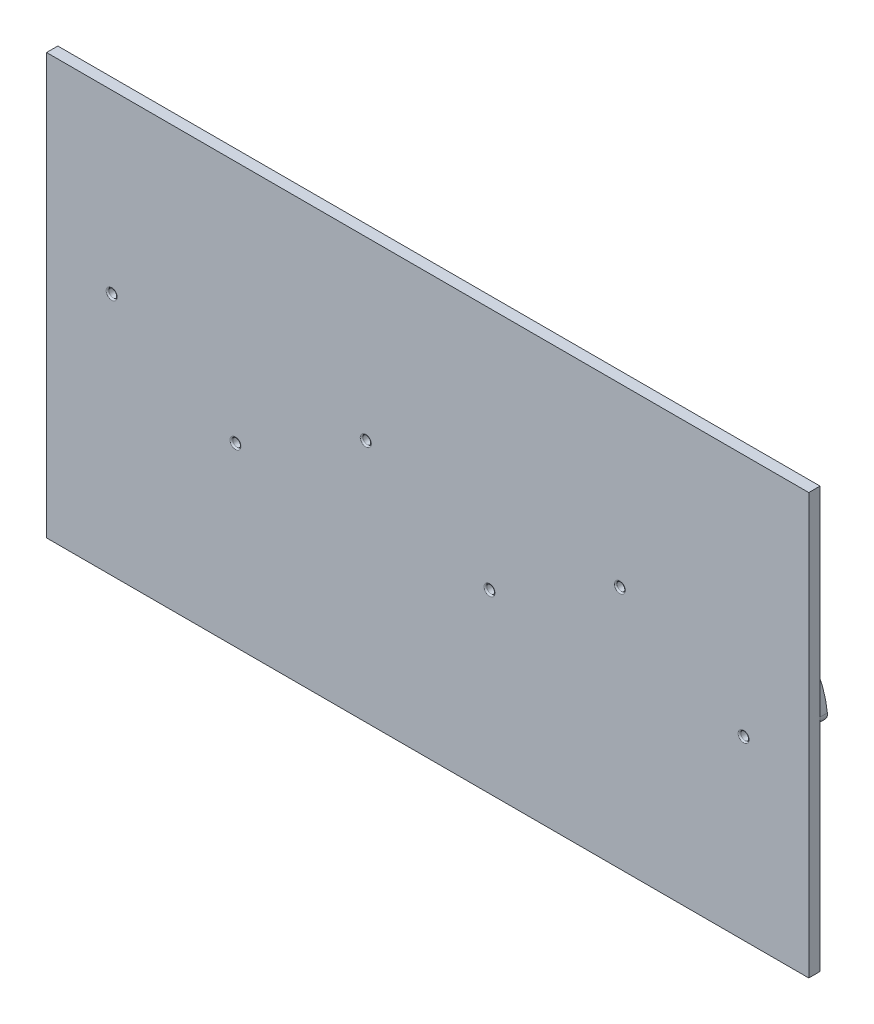
SolidWorks part; units mm, degrees
ref_plane "Front" through (0, 0, 0) normal (0, 0, 1) x (1, 0, 0)
ref_plane "Top" through (0, 0, 0) normal (0, 1, 0) x (1, 0, 0)
ref_plane "Right" through (0, 0, 0) normal (1, 0, 0) x (0, 0, -1)
sketch "Sketch1" plane through (0, 0, 0) normal (0, 0, 1) x (1, 0, 0)
  line L0 (0, 0) -> (0, 155.4998) construction
  line L1 (0, 0) -> (0, -147.6375) construction
  line L2 (0, 25.4) -> (-281.6343, 25.4) construction
  line L3 (0, -25.4) -> (-306.3875, -25.4) construction
  line L4 (-92.1, 25.4) -> (-92.1, -160.4472) construction
  line L5 (0, 25.4) -> (-92.1, 25.4)
  line L6 (-92.1, 25.4) -> (-92.1, -25.4)
  line L7 (-92.1, -25.4) -> (0, -25.4)
  line L8 (0, -25.4) -> (0, 25.4)
  point P3 (0, 25.4)
  point P5 (0, -25.4)
  point P11 (-92.1, 25.4)
  point P14 (-92.1, -25.4)
  dimension "D1" = 25.4
  dimension "W" = 25.4
  dimension "Len" = 92.1
extrude "Extrude1" add sketch "Sketch1" along normal blind 1.36
sketch "Sketch2" plane through (0, 0, 0) normal (0, 0, -1) x (-1, 0, 0)
  line L0 (0, 0) -> (98.425, 0) construction
  line L1 (0.05, 0) -> (2, 0)
  line L2 (10.2333, 10.1833) -> (10.2333, 8.2333)
  line L3 (15.35, 0) -> (15.35, 29.0677) construction
  line L4 (15.35, 15.35) -> (-21.7206, 15.35) construction
  line L5 (15.3, 15.35) -> (13.35, 15.35)
  line L6 (10.2333, 12.2333) -> (10.2333, 10.2833)
  line L7 (15.35, 15.35) -> (104.1914, 15.35) construction
  line L8 (15.4, 15.35) -> (17.35, 15.35)
  line L9 (22.8284, 4.0716) -> (21.4495, 5.4505)
  line L10 (11.55, 15.35) -> (126.7382, -99.8382) construction
  line L11 (11.55, 15.35) -> (11.55, -99.8382) construction
  line L12 (15.35, 0) -> (15.35, -83.1764) construction
  line L13 (15.35, -15.35) -> (117.3684, -15.35) construction
  line L14 (15.35, -15.35) -> (-8.0572, -15.35) construction
  line L15 (19.15, -15.35) -> (19.15, 75.8167) construction
  line L16 (19.15, -15.35) -> (-67.4264, 71.2264) construction
  line L17 (7.8716, -4.0716) -> (9.2505, -5.4505)
  line L18 (13.35, -15.35) -> (15.3, -15.35)
  line L19 (15.4, -15.35) -> (17.35, -15.35)
  line L20 (20.4667, -12.2333) -> (20.4667, -10.2833)
  line L21 (20.4667, -10.1833) -> (20.4667, -8.2333)
  line L22 (28.7, 0) -> (30.65, 0)
  arc A0 (0.05, 0) -> (10.2333, 10.1833) centre (10.2333, 0) cw
  arc A1 (15.3, 15.35) -> (10.2333, 10.2833) centre (10.2333, 15.35) cw
  arc A2 (2, 0) -> (10.2333, 8.2333) centre (10.2333, 0) cw
  arc A3 (10.2333, 12.2333) -> (13.35, 15.35) centre (10.2333, 15.35) ccw
  arc A4 (15.4, 15.35) -> (27.5, 15.35) centre (21.45, 15.35) cw
  arc A5 (17.35, 15.35) -> (25.55, 15.35) centre (21.45, 15.35) cw
  circle A6 centre (11.55, 15.35) radius 16 construction
  arc A7 (25.55, 15.35) -> (21.4495, 5.4505) centre (11.55, 15.35) cw
  arc A8 (27.5, 15.35) -> (22.8284, 4.0716) centre (11.55, 15.35) cw
  arc A9 (30.65, 0) -> (20.4667, -10.1833) centre (20.4667, 0) cw
  arc A10 (28.7, 0) -> (20.4667, -8.2333) centre (20.4667, 0) cw
  arc A11 (15.4, -15.35) -> (20.4667, -10.2833) centre (20.4667, -15.35) cw
  arc A12 (17.35, -15.35) -> (20.4667, -12.2333) centre (20.4667, -15.35) cw
  arc A13 (15.3, -15.35) -> (3.2, -15.35) centre (9.25, -15.35) cw
  arc A14 (13.35, -15.35) -> (5.15, -15.35) centre (9.25, -15.35) cw
  arc A15 (3.2, -15.35) -> (7.8716, -4.0716) centre (19.15, -15.35) cw
  arc A16 (5.15, -15.35) -> (9.2505, -5.4505) centre (19.15, -15.35) cw
  point P3 (30.7, 0)
  point P4 (61.4, 0)
  point P5 (92.1, 0)
  point P6 (15.35, 0)
  point P7 (46.05, 0)
  point P8 (76.75, 0)
  point P9 (10.2333, 0)
  point P10 (20.4667, 0)
  point P11 (40.9333, 0)
  point P12 (51.1667, 0)
  point P13 (71.6333, 0)
  point P14 (81.8667, 0)
  point P19 (15.35, 15.35)
  point P25 (10.2333, 15.35)
  point P31 (21.45, 15.35)
  point P38 (11.55, 15.35)
  point P50 (15.35, -15.35)
  point P54 (20.4667, -15.35)
  point P60 (9.25, -15.35)
  point P67 (19.15, -15.35)
  dimension "D11" = 10.1833
  dimension "D12" = 15.35
  dimension "D13" = 8.2333
  dimension "D14" = 5.1167
  dimension "D15" = 5.0667
  dimension "D16" = 3.1167
  dimension "D17" = 6.05
  dimension "D18" = 4.1
  dimension "D20" = 10.1833
  dimension "Dia3" = 32
  dimension "D21" = 8.2333
  dimension "D24" = 5.0667
  dimension "D25" = 3.1167
  dimension "D27" = 6.05
  dimension "D28" = 4.1
  dimension "D1" = 30.7
  dimension "pitch" = 30.7
  dimension "D2" = 15.35
  dimension "D3" = 15.35
  dimension "D4" = 15.35
  dimension "D5" = 10.2333
  dimension "D6" = 10.2333
  dimension "D7" = 10.2333
  dimension "D8" = 10.2333
  dimension "D9" = 10.2333
  dimension "D10" = 10.2333
  dimension "R2" = 6.1
  dimension "D19" = 45
  dimension "R3mR2mR2" = 3.8
  dimension "D22" = 15.35
  dimension "D23" = 5.1167
  dimension "D26" = 6.1
  dimension "D29" = 3.8
  dimension "D30" = 45
extrude "Extrude2" add sketch "Sketch2" along normal blind 1
sketch "Sketch3" plane through (0, 0, 1.36) normal (0, 0, 1) x (1, 0, 0)
  line L0 (-0.05, 0) -> (-101.6, 0) construction
  point P4 (-30.75, 0)
  point P5 (-61.45, 0)
  point P6 (-15.4, 0)
  point P7 (-46.1, 0)
  point P8 (-76.8, 0)
  point P9 (-10.2833, 0)
  point P10 (-20.5167, 0)
  point P11 (-40.9833, 0)
  point P12 (-56.3333, 0)
  point P13 (-71.6833, 0)
  point P14 (-81.9167, 0)
  point P15 (-92.15, 0)
  dimension "D1" = 30.7
  dimension "D2" = 30.7
  dimension "D3" = 15.35
  dimension "D4" = 15.35
  dimension "D5" = 15.35
  dimension "D6" = 10.2333
  dimension "D7" = 10.2333
  dimension "D8" = 10.2333
  dimension "D9" = 10.2333
  dimension "D10" = 10.2333
  dimension "D11" = 30.7
  dimension "D12" = 10.2333
fillet "Fillet1" radius 1 10 edges at (-30.65, 0, -0.5) (-10.2333, 10.1833, -0.5) (-15.3, -15.35, -0.5) (-15.4, -15.35, -0.5) (-20.4667, -10.2833, -0.5) (-20.4667, -10.1833, -0.5) (-10.2333, 10.2833, -0.5) (-15.3, 15.35, -0.5) (-15.4, 15.35, -0.5) (-0.05, 0, -0.5)
sketch "Sketch5" plane through (0, 0, 0) normal (0, 0, -1) x (-1, 0, 0)
  circle A0 centre (22.8284, 4.0716) radius 0.5
  circle A1 centre (7.8716, -4.0716) radius 0.5
  point P0 (22.8284, 4.0716)
  point P1 (7.8716, -4.0716)
extrude "Extrude3" cut sketch "Sketch5" against normal through all
fillet "Fillet2" radius 1.5 2 edges at (-22.8284, 4.0716, -0.5) (-7.8716, -4.0716, -0.5)
fillet "Fillet3" radius 0.17 4 edges at (-8.3716, -4.0716, 0) (-23.3284, 4.0716, 0) (-23.3284, 4.0716, 1.36) (-8.3716, -4.0716, 1.36)
sketch "Sketch6" plane through (0, 0, 0) normal (0, 0, -1) x (-1, 0, 0)
  line L0 (-23.8125, 0) -> (114.3, 0) construction
pattern_linear "LPattern3" count 3 spacing 30.7 along (-1, 0, 0) of "Fillet3", "Extrude3", "Extrude2", "Fillet1", "Fillet2"
equation "\"D1@Sketch1\" = \"W\""
equation "\"D1@Sketch2\" = \"pitch\""
equation "\"D2@Sketch2\" = \"pitch\"/2"
equation "\"D3@Sketch2\" = \"pitch\"/2"
equation "\"D4@Sketch2\" = \"pitch\"/2"
equation "\"D5@Sketch2\" = \"pitch\"/3"
equation "\"D6@Sketch2\" = \"pitch\"/3"
equation "\"D7@Sketch2\" = \"pitch\"/3"
equation "\"D8@Sketch2\" = \"pitch\"/3"
equation "\"D9@Sketch2\" = \"pitch\"/3"
equation "\"D10@Sketch2\" = \"pitch\"/3"
equation "\"D11@Sketch2\" = \"pitch\"/3-0.05"
equation "\"D13@Sketch2\" = \"pitch\"/3 -2"
equation "\"D1@Sketch3\" = \"pitch\""
equation "\"D2@Sketch3\" = \"pitch\""
equation "\"D3@Sketch3\" = \"pitch\"/2"
equation "\"D4@Sketch3\" = \"pitch\"/2"
equation "\"D5@Sketch3\" = \"pitch\"/2"
equation "\"D6@Sketch3\" = \"pitch\"/3"
equation "\"D7@Sketch3\" = \"pitch\"/3"
equation "\"D8@Sketch3\" = \"pitch\"/3"
equation "\"D9@Sketch3\" = \"pitch\"/3"
equation "\"D10@Sketch3\" = \"pitch\"/3"
equation "\"D11@Sketch3\" = \"pitch\""
equation "\"D12@Sketch3\" = \"pitch\"/3"
equation "\"D12@Sketch2\" = \"pitch\"/2"
equation "\"D14@Sketch2\" = \"pitch\"/6"
equation "\"D15@Sketch2\" = \"pitch\"/6-0.05"
equation "\"D16@Sketch2\" = \"pitch\"/6-2"
equation "\"D17@Sketch2\" = \"R2\"-0.05"
equation "\"D18@Sketch2\" = \"R2\"-2"
equation "\"D20@Sketch2\" = \"pitch\"/3-0.05"
equation "\"D21@Sketch2\" = \"pitch\"/3-2"
equation "\"D22@Sketch2\" = \"pitch\"/2"
equation "\"D23@Sketch2\" = \"pitch\"/6"
equation "\"D24@Sketch2\" = \"pitch\"/6-0.05"
equation "\"D25@Sketch2\" = \"pitch\"/6-2"
equation "\"D26@Sketch2\" = \"R2\""
equation "\"D27@Sketch2\" = \"R2\"-0.05"
equation "\"D28@Sketch2\" = \"R2\"-2"
equation "\"D29@Sketch2\" = \"R3mR2mR2\""
